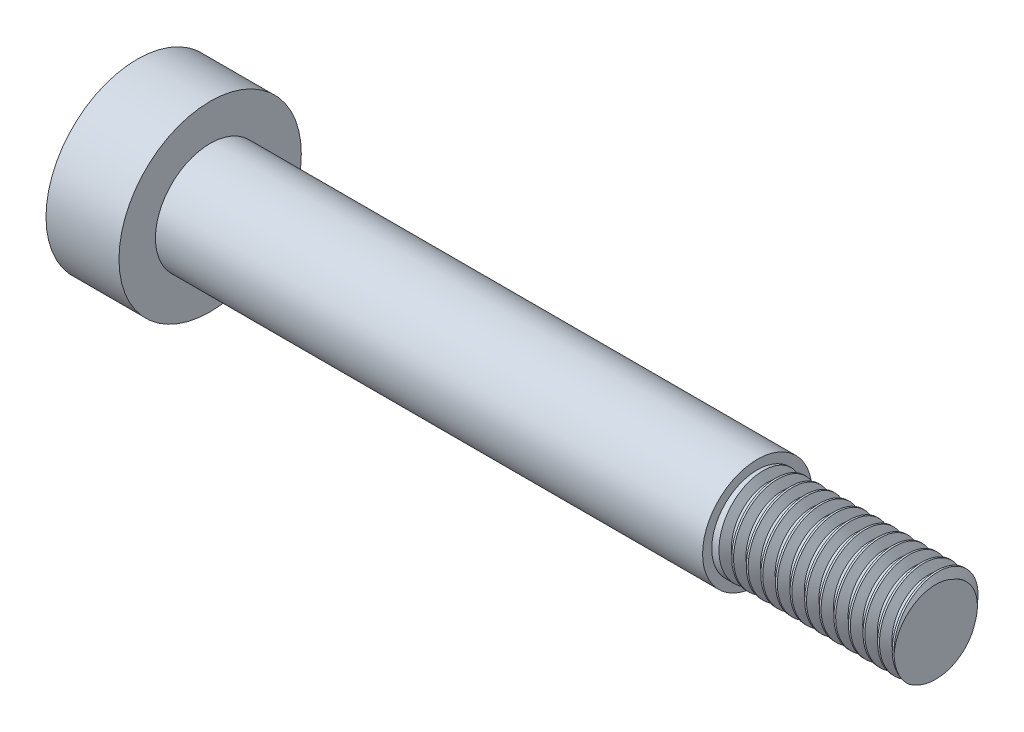
SolidWorks part; units mm, degrees
ref_plane "Front" through (0, 0, 0) normal (0, 0, 1) x (1, 0, 0)
ref_plane "Top" through (0, 0, 0) normal (0, 1, 0) x (1, 0, 0)
ref_plane "Right" through (0, 0, 0) normal (1, 0, 0) x (0, 0, -1)
sketch "草图1" plane through (0, 0, 0) normal (0, 0, 1) x (1, 0, 0)
  line L0 (-10.9542, 0) -> (34.0362, 0) construction
  line L1 (0, 0) -> (44, 0)
  line L2 (44, 0) -> (44, 2.5)
  line L3 (44, 2.5) -> (34, 2.5)
  line L4 (34, 2.5) -> (34, 3)
  line L5 (34, 3) -> (4, 3)
  line L6 (4, 3) -> (4, 5)
  line L7 (4, 5) -> (0, 5)
  line L8 (0, 5) -> (0, 0)
  dimension "D1" = 5
  dimension "D2" = 3
  dimension "D3" = 2.5
  dimension "D4" = 4
  dimension "D5" = 30
  dimension "D6" = 10
revolve "旋转1" add sketch "草图1" angle 360 about L0
sketch "草图2" plane through (0, 0, 0) normal (-1, 0, 0) x (0, 0, 1)
  line L1 (0, 1.7321) -> (-1.5, 0.866)
  line L2 (-1.5, 0.866) -> (-1.5, -0.866)
  line L3 (-1.5, -0.866) -> (0, -1.7321)
  line L4 (0, -1.7321) -> (1.5, -0.866)
  line L5 (1.5, -0.866) -> (1.5, 0.866)
  line L6 (1.5, 0.866) -> (0, 1.7321)
  circle A0 centre (0, 0) radius 1.5 construction
  dimension "D1" = 3
extrude "切除-拉伸1" cut sketch "草图2" against normal blind 2.5
thread "螺纹线1" pitch 0.8 method cut profile "螺纹线轮廓1" start angle 0, offset 0, length 10, pitch 0.8, diameter 5
ref_plane "基准面1" through (34, 0, -2.5) normal (0, -1, 0) x (0, 0, -1)
sketch "螺纹线轮廓1" plane through (34, 0, -2.5) normal (0, -1, 0) x (0, 0, -1)
  line L0 (0, 0) -> (0, 0.8) construction
  line L11 (0, 0) -> (0, 0.7)
  line L12 (0, 0.7) -> (-0.433, 0.45)
  line L13 (-0.433, 0.45) -> (-0.433, 0.25)
  line L15 (-0.433, 0.25) -> (0, 0)
  line L17 (-0.433, 0.35) -> (0, 0.35) construction
  point P2 (0, 0)
  dimension "Pitch" = 0.8
  dimension "Profile_Angle" = 60
  dimension "Profile_Land" = 0.2
  dimension "Profile_Height" = 0.433
